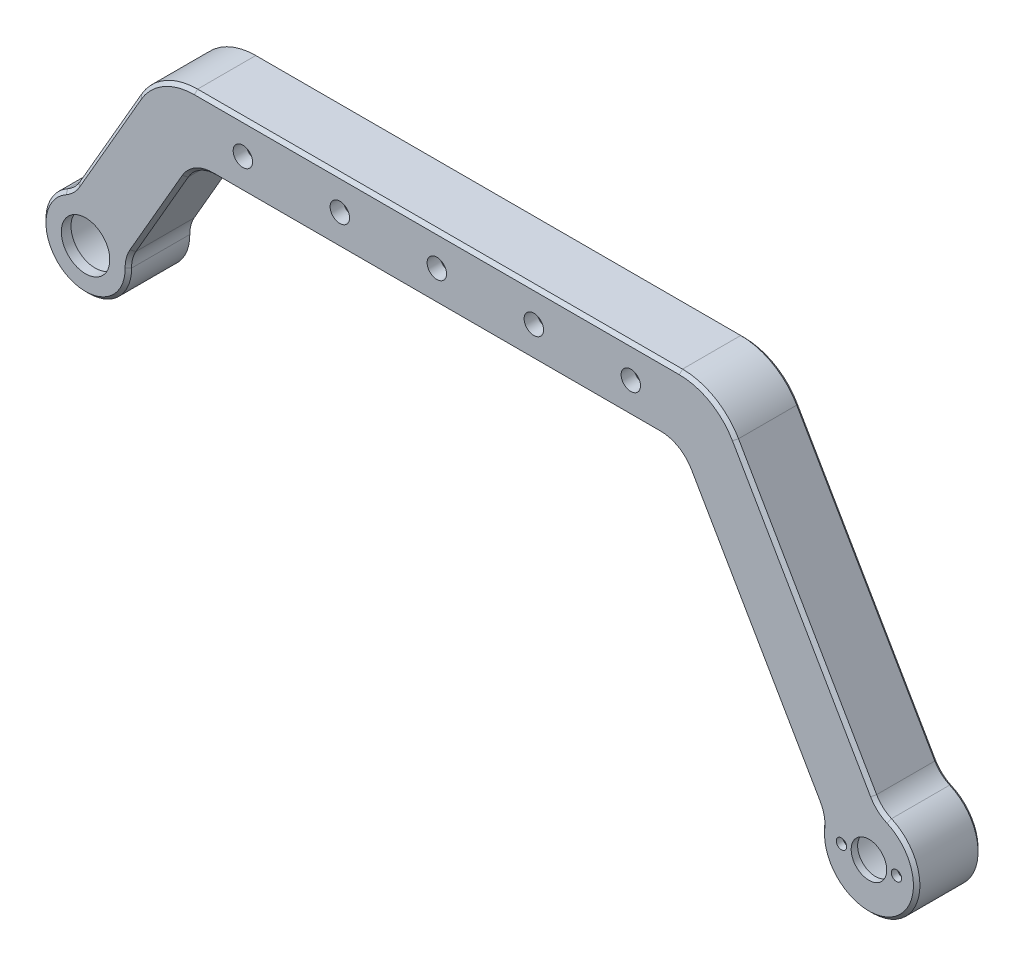
SolidWorks part; units mm, degrees
ref_plane "Front Plane" through (0, 0, 0) normal (0, 0, 1) x (1, 0, 0)
ref_plane "Top Plane" through (0, 0, 0) normal (0, 1, 0) x (1, 0, 0)
ref_plane "Right Plane" through (0, 0, 0) normal (1, 0, 0) x (0, 0, -1)
ref_axis "X" through (-88.99, 0, 0) along (1, 0, 0)
ref_axis "Y" through (0, 55, 0) along (0, -1, 0)
ref_axis "Z" through (0, 0, -88.99) along (0, 0, 1)
sketch "Sketch1" plane through (0, 0, 0) normal (0, 0, 1) x (1, 0, 0)
  line L0 (-75, -10) -> (75, -10)
  line L1 (-75, 10) -> (75, 10)
  line L3 (125, -96.6025) -> (75, -10)
  line L4 (-75, -10) -> (-100, -53.3013)
  line L5 (-117.3205, -43.3013) -> (-92.3205, 0)
  line L6 (92.3205, 0) -> (142.3205, -86.6025)
  line L7 (0, 10) -> (0, -10) construction
  line L8 (0, 0) -> (-30, 0) construction
  line L9 (0, 0) -> (30, 0) construction
  line L10 (30, 0) -> (60, 0) construction
  line L11 (-30, 0) -> (-60, 0) construction
  arc A0 (142.3205, -86.6025) -> (125, -96.6025) centre (133.6603, -91.6025) cw
  arc A1 (-100, -53.3013) -> (-117.3205, -43.3013) centre (-108.6603, -48.3013) cw
  arc A2 (-92.3205, 0) -> (-75, 10) centre (-75, -10) cw
  arc A3 (75, 10) -> (92.3205, 0) centre (75, -10) cw
  circle A4 centre (0, 0) radius 1.6
  circle A5 centre (-60, 0) radius 1.6
  circle A6 centre (-30, 0) radius 1.6
  circle A7 centre (30, 0) radius 1.6
  circle A8 centre (60, 0) radius 1.6
  point P3 (0, 0)
  dimension "D1" = 150
  dimension "D7" = 3.2
  dimension "D8" = 30
  dimension "D2" = 20
  dimension "D3" = 100
  dimension "D4" = 50
  dimension "D5" = 60
  dimension "D6" = 60
extrude "Boss-Extrude1" add sketch "Sketch1" along normal mid plane 20
sketch "Sketch2" plane through (0, 0, 0) normal (0, 0, 1) x (1, 0, 0)
  line L0 (125.1603, -91.6025) -> (142.1603, -91.6025) construction
  circle A0 centre (-108.6603, -48.3013) radius 11.25
  circle A1 centre (-108.6603, -48.3013) radius 13.25
  circle A2 centre (-108.6603, -48.3013) radius 7.5
  circle A3 centre (133.6603, -91.6025) radius 12.75
  circle A4 centre (133.6603, -91.6025) radius 14.75
  circle A5 centre (133.6603, -91.6025) radius 5.5
  circle A6 centre (142.1603, -91.6025) radius 1.6
  circle A7 centre (125.1603, -91.6025) radius 1.6
  point P14 (133.6603, -91.6025)
  dimension "D1" = 22.5
  dimension "D3" = 15
  dimension "D4" = 25.5
  dimension "D6" = 11
  dimension "D7" = 3.2
  dimension "D8" = 17
  dimension "D2" = 2
  dimension "D5" = 2
extrude "Cut-Extrude1" cut sketch "Sketch2" against normal through all both and the other way through all contours A0 | A3
extrude "Boss-Extrude2" add sketch "Sketch2<3>" along normal up to surface (10 mm away) and the other way up to surface (10 mm away) contours A1 A0 region at (-121.5355, -48.3013, 0) up to face at (4.7872, -24.3069, 10) other way up to face at (4.7872, -24.3069, -10)
sketch "Sketch2<3>" plane through (0, 0, 0) normal (0, 0, 1) x (1, 0, 0) same geometry as "Sketch2"
extrude "Boss-Extrude3" add sketch "Sketch2<4>" against normal blind 3 from surface contours A0 A2 region at (-119.5921, -48.3013, 0) starting at face at (3.7392, -26.1222, 10)
sketch "Sketch2<4>" plane through (0, 0, 0) normal (0, 0, 1) x (1, 0, 0) same geometry as "Sketch2"
extrude "Boss-Extrude4" add sketch "Sketch2<5>" along normal up to surface (10 mm away) and the other way up to surface (10 mm away) contours A4 A3 region at (119.3274, -91.6025, 0) up to face at (3.7392, -26.1222, 10) other way up to face at (3.7392, -26.1222, -10)
sketch "Sketch2<5>" plane through (0, 0, 0) normal (0, 0, 1) x (1, 0, 0) same geometry as "Sketch2"
extrude "Boss-Extrude5" add sketch "Sketch2<6>" against normal blind 2 from surface contours A3 A7 A5 A6 region at (121.2709, -91.6025, 0) starting at face at (4.9675, -28.2497, 10)
sketch "Sketch2<6>" plane through (0, 0, 0) normal (0, 0, 1) x (1, 0, 0) same geometry as "Sketch2"
fillet "Fillet1" radius 10 6 edges at (136.8992, -77.2126, 0) (-112.9742, -35.7732, 0) (-95.6537, -45.7732, 0) (119.5787, -87.2126, 0) (75, -10, 0) (-75, -10, 0)
sketch "Sketch3" plane through (0, 0, 0) normal (0, 0, 1) x (1, 0, 0)
  circle A0 centre (-60, 0) radius 3
  circle A1 centre (-30, 0) radius 3
  circle A2 centre (0, 0) radius 3
  circle A3 centre (30, 0) radius 3
  circle A4 centre (60, 0) radius 3
  dimension "D1" = 6
extrude "Cut-Extrude2" cut sketch "Sketch3" against normal blind 4 from surface starting at face at (6.0699, -34.2604, 10)
chamfer "Chamfer1" distance 1 angle 45 32 edges at (0, -10, -10) (74.2265, -11.3397, -10) (-74.2265, -11.3397, -10) (97.7985, -49.4882, -10) (-85.9794, -29.0169, -10) (118.8331, -86.905, -10) (-95.0858, -45.5012, -10) (141.0353, -104.3764, -10) (-115.2853, -59.7761, -10) (137.0056, -76.4131, -10) (-113.0225, -35.1454, -10) (113.6756, -36.9882, -10) (-101.8565, -16.5169, -10) (85, 7.3205, -10) (-85, 7.3205, -10) (0, 10, -10) (0, -10, 10) (74.2265, -11.3397, 10) (-74.2265, -11.3397, 10) (97.7985, -49.4882, 10) (-85.9794, -29.0169, 10) (118.8331, -86.905, 10) (-95.0858, -45.5012, 10) (141.0353, -104.3764, 10) (-115.2853, -59.7761, 10) (137.0056, -76.4131, 10) (-113.0225, -35.1454, 10) (113.6756, -36.9882, 10) (-101.8565, -16.5169, 10) (85, 7.3205, 10) (-85, 7.3205, 10) (0, 10, 10)
mirror "Mirror1" [suppressed] about plane through (0, 0, 0) normal (0, 0, 1) of bodies 106
delete or keep bodies "Body-Delete/Keep 1" [suppressed] type keep bodies bodies 107
